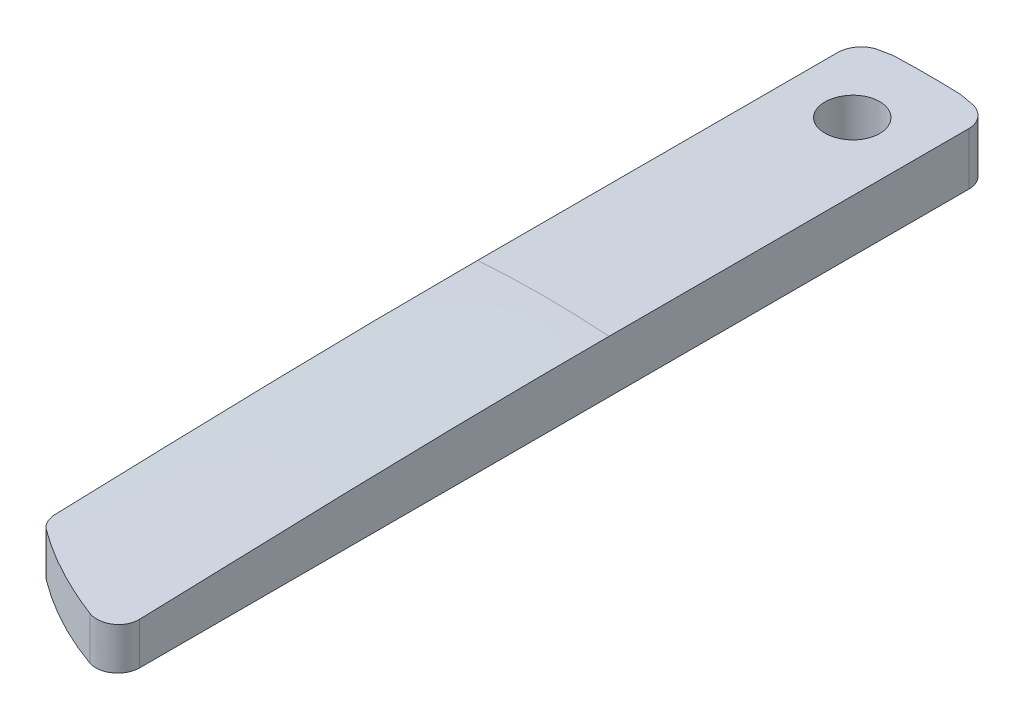
SolidWorks part; units mm, degrees
ref_plane "Front Plane" through (0, 0, 0) normal (0, 0, 1) x (1, 0, 0)
ref_plane "Top Plane" through (0, 0, 0) normal (0, 1, 0) x (1, 0, 0)
ref_plane "Right Plane" through (0, 0, 0) normal (1, 0, 0) x (0, 0, -1)
sketch "Sketch2" plane through (0, 0, 0) normal (0, 1, 0) x (1, 0, 0)
  line L0 (-6, -49.7307) -> (-6, 24.2693)
  line L1 (6, 24.2693) -> (6, -55.7307)
  arc A0 (-6, 24.2693) -> (6, 24.2693) centre (0, 0) cw
  arc A1 (6, -55.7307) -> (-6, -49.7307) centre (13.9929, -24.745) cw
  circle A2 centre (0, 18) radius 2.5
  point P6 (0, 0)
  point P8 (0, 17.8281)
  dimension "D2" = 25
  dimension "D5" = 32
  dimension "D6" = 5
  dimension "D1" = 6
  dimension "D3" = 12
  dimension "D4" = 80
  dimension "D7" = 18
extrude "Boss-Extrude1" add sketch "Sketch2" along normal mid plane 5
fillet "Fillet1" radius 2 4 edges at (6, 0, 55.7307) (-6, 0, 49.7307) (-6, 0, -24.2693) (6, 0, -24.2693)
sketch "Sketch4" plane through (0, 0, 0) normal (1, 0, 0) x (0, 0, -1)
  line L0 (24.8095, 2.5) -> (-10.1905, 2.5)
  line L1 (25, 2.5) -> (24.619, 2.5) construction
  line L2 (-53.0318, 2.5) -> (22.6495, 2.5) construction
  line L3 (-55.0318, 2.5) -> (-55.0318, -2.5) construction
  line L4 (-55.0318, -2.5) -> (-53.0318, -2.5) construction
  line L5 (-77.3565, -82.5) -> (81.7653, -82.5) construction
  line L6 (-55.0318, 1.5) -> (-55.0318, -82.5)
  line L7 (24.8095, 2.5) -> (24.8095, -82.5)
  spline S0 degree 3 poles (-10.1905, 2.5) (-25.8107, 2.5) (-40.0094, 1.9629) (-55.0318, 1.5) knots 0 0 0 0 1 1 1 1
  dimension "D3" = 30
  dimension "D1" = 4
  dimension "D2" = 16
  dimension "D4" = 35
  dimension "D5" = 0.5
  dimension "D6" = 85
surface "Surface-Revolve1" sketch "Sketch4" parameters "D1"=360
other "SurfaceCut1" flip cut yes
